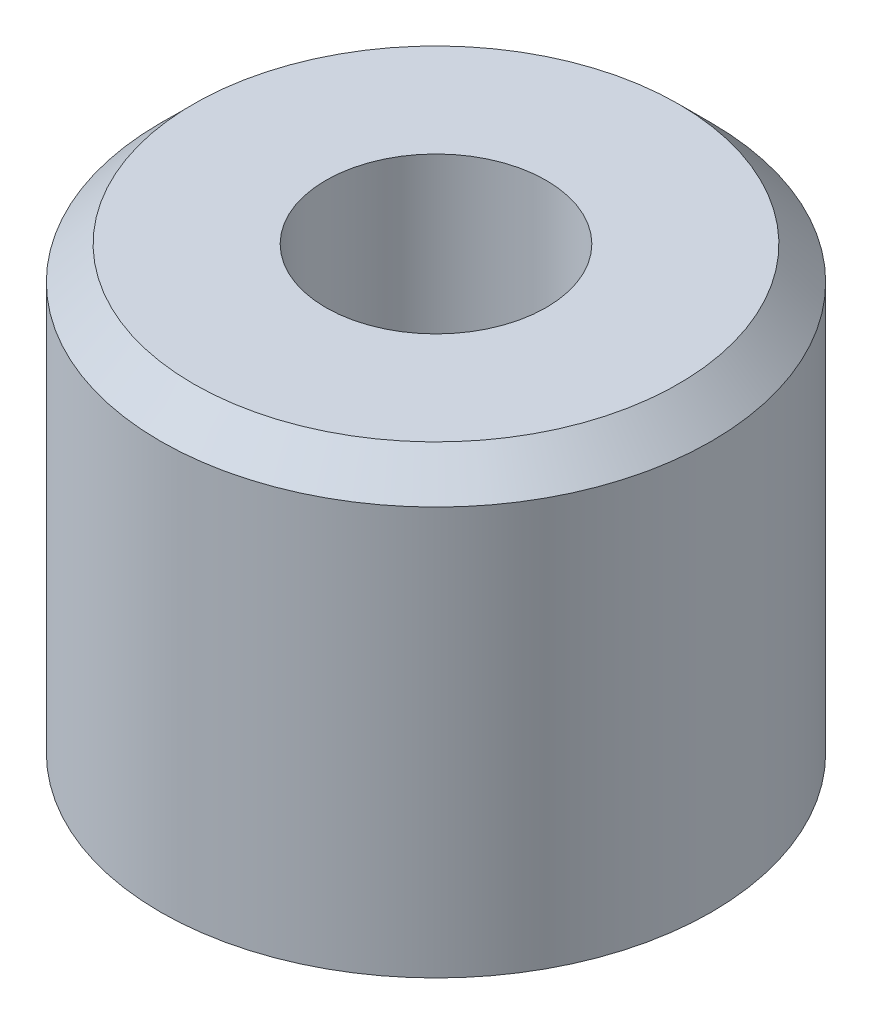
SolidWorks part; units mm, degrees
ref_plane "Front Plane" through (0, 0, 0) normal (0, 0, 1) x (1, 0, 0)
ref_plane "Top Plane" through (0, 0, 0) normal (0, 1, 0) x (1, 0, 0)
ref_plane "Right Plane" through (0, 0, 0) normal (1, 0, 0) x (0, 0, -1)
sketch "Sketch1" plane through (0, 0, 0) normal (0, 1, 0) x (1, 0, 0)
  circle A0 centre (0, 0) radius 63.5
  dimension "D1" = 127
extrude "Boss-Extrude1" add sketch "Sketch1" along normal blind 101.6
sketch "Sketch2" plane through (0, 101.6, 0) normal (0, 1, 0) x (1, 0, 0)
  circle A0 centre (0, 0) radius 25.4
  dimension "D1" = 50.8
extrude "Cut-Extrude1" cut sketch "Sketch2" against normal blind 88.9
fillet "Fillet1" radius 7.62 1 edges at (0, 101.6, 63.5) profile chamfer
